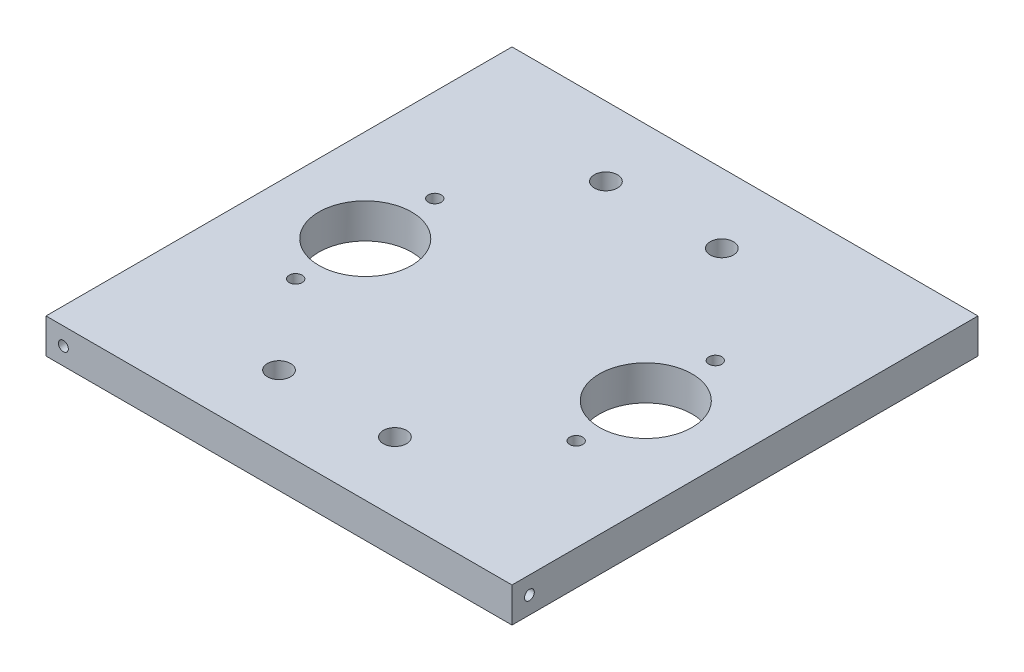
SolidWorks part; units mm, degrees
material "6061-T6 (SS)"
ref_plane "Front" through (0, 0, 0) normal (0, 0, 1) x (1, 0, 0)
ref_plane "Top" through (0, 0, 0) normal (0, 1, 0) x (1, 0, 0)
ref_plane "Right" through (0, 0, 0) normal (1, 0, 0) x (0, 0, -1)
sketch "Sketch1" plane through (0, 0, 0) normal (0, 1, 0) x (1, 0, 0)
  line L1 (0, 0) -> (127.635, 0)
  line L2 (0, 0) -> (0, 127.635)
  line L3 (0, 127.635) -> (127.635, 127.635)
  line L4 (127.635, 0) -> (127.635, 127.635)
  dimension "D1" = 127.635
  dimension "D2" = 127.635
extrude "Main Plate" add sketch "Sketch1" along normal blind 9.525
sketch "Sketch2" plane through (0, 9.525, 0) normal (0, 1, 0) x (1, 0, 0)
  line L0 (0, 127.635) -> (0, 0) construction
  line L1 (127.635, 127.635) -> (0, 127.635) construction
  circle A0 centre (44.7675, 108.585) radius 3.175
  dimension "D1" = 6.35
  dimension "D2" = 44.7675
  dimension "D3" = 19.05
extrude "U-Bolt Hole" cut sketch "Sketch2" against normal blind 12.7
pattern_linear "U-Bolt Pattern" count 2 spacing 31.75 along (1, 0, 0) count 2 spacing 89.535 along (0, 0, 1) of "U-Bolt Hole"
sketch "Sketch3" plane through (0, 9.525, 0) normal (0, 1, 0) x (1, 0, 0)
  line L0 (0, 127.635) -> (0, 0) construction
  line L1 (0, 0) -> (127.635, 0) construction
  circle A0 centre (25.4, 42.9895) radius 1.778
  dimension "D1" = 3.556
  dimension "D2" = 25.4
  dimension "D3" = 42.9895
extrude "Raptor Bolt Hole" cut sketch "Sketch3" against normal blind 12.7
pattern_linear "Raptor Bolt Pattern" count 2 spacing 38.1 along (0, 0, -1) count 2 spacing 76.835 along (1, 0, 0) of "Raptor Bolt Hole"
sketch "Sketch4" plane through (0, 9.525, 0) normal (0, 1, 0) x (1, 0, 0)
  line L0 (0, 127.635) -> (0, 0) construction
  circle A0 centre (25.4, 62.0395) radius 12.7
  dimension "D1" = 25.4
  dimension "D2" = 19.05
  dimension "D3" = 25.4
extrude "Co2 Cylinder Hole" cut sketch "Sketch4" against normal blind 12.7
pattern_linear "Co2 Pattern" count 2 spacing 76.835 along (1, 0, 0) of "Co2 Cylinder Hole"
sketch "Sketch5" plane through (0, 0, 0) normal (0, 0, 1) x (1, 0, 0)
  line L0 (0, 9.525) -> (0, 0) construction
  line L1 (0, 0) -> (127.635, 0) construction
  circle A0 centre (4.7625, 4.7625) radius 1.3526
  dimension "D1" = 2.7051
  dimension "D2" = 4.7625
  dimension "D3" = 4.7625
extrude "Frame attachment hole 1" cut sketch "Sketch5" against normal blind 12.7
sketch "Sketch6" plane through (0, 0, 0) normal (-1, 0, 0) x (0, 0, 1)
  line L2 (-127.635, 0) -> (0, 0) construction
  line L3 (-127.635, 9.525) -> (-127.635, 0) construction
  circle A0 centre (-122.8725, 4.7625) radius 1.3525
  dimension "D1" = 2.7051
  dimension "D2" = 4.7625
  dimension "D3" = 4.7625
extrude "Frame attachment hole 2" cut sketch "Sketch6" against normal blind 12.7
sketch "Sketch7" plane through (0, 0, -127.635) normal (0, 0, -1) x (-1, 0, 0)
  line L2 (-127.635, 0) -> (0, 0) construction
  line L3 (-127.635, 9.525) -> (-127.635, 0) construction
  circle A0 centre (-122.8725, 4.7625) radius 1.3525
  dimension "D1" = 2.7051
  dimension "D2" = 4.7625
  dimension "D3" = 4.7625
extrude "Frame attachment hole 3" cut sketch "Sketch7" against normal blind 12.7
sketch "Sketch8" plane through (127.635, 0, 0) normal (1, 0, 0) x (0, 0, -1)
  line L2 (0, 0) -> (127.635, 0) construction
  line L3 (0, 9.525) -> (0, 0) construction
  circle A0 centre (4.7625, 4.7625) radius 1.3526
  dimension "D1" = 2.7051
  dimension "D2" = 4.7625
  dimension "D3" = 4.7625
extrude "Frame attachment hole 4" cut sketch "Sketch8" against normal blind 12.7
